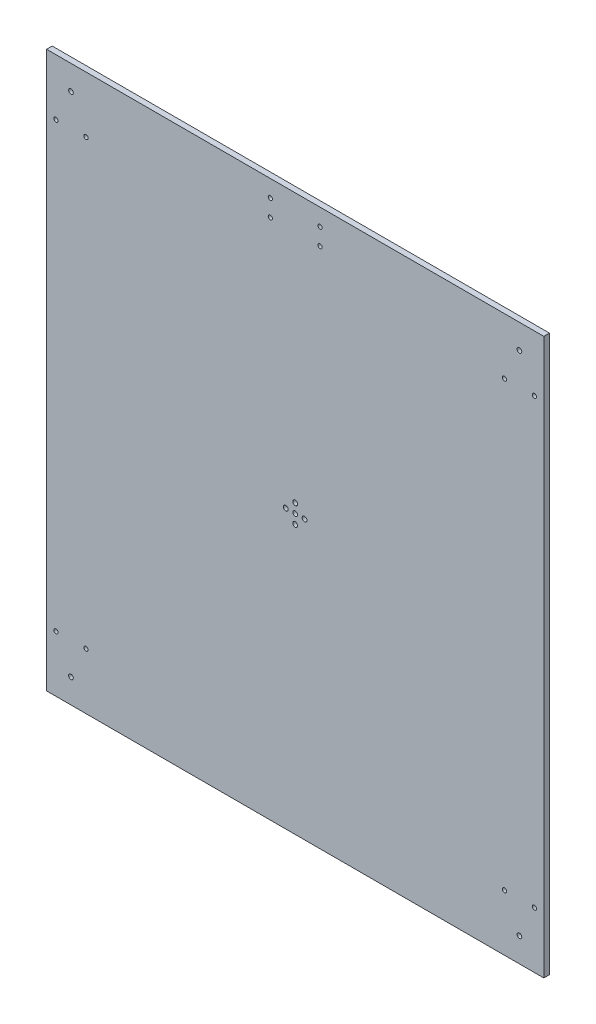
SolidWorks part; units mm, degrees
ref_plane "Спереди" through (0, 0, 0) normal (0, 0, 1) x (1, 0, 0)
ref_plane "Сверху" through (0, 0, 0) normal (0, 1, 0) x (1, 0, 0)
ref_plane "Справа" through (0, 0, 0) normal (1, 0, 0) x (0, 0, -1)
sketch "Эскиз3" plane through (0, 0, 0) normal (0, 0, 1) x (1, 0, 0)
  line L0 (0, 0) -> (0, 10) construction
  line L5 (265, -296.15) -> (-265, -296.15)
  line L6 (265, -296.15) -> (265, 296.15)
  line L7 (265, 296.15) -> (-265, 296.15)
  line L8 (-265, -296.15) -> (-265, 296.15)
  line L9 (0, 0) -> (10, 0) construction
  line L10 (0, 0) -> (0, -10) construction
  line L11 (0, 0) -> (-10, 0) construction
  circle A0 centre (0, 0) radius 2.55
  circle A1 centre (0, 10) radius 2.55
  circle A2 centre (10, 0) radius 2.55
  circle A3 centre (0, -10) radius 2.55
  circle A4 centre (-10, 0) radius 2.55
  point P0 (0, 0)
  point P5 (-265, 0)
  point P6 (0, 296.15)
  point P21 (0, 0)
  dimension "D3" = 5.1
  dimension "D4" = 5.1
  dimension "D1" = 592.3
  dimension "D2" = 530
  dimension "D5" = 10
  dimension "D6" = 4
extrude "Бобышка-Вытянуть1" add sketch "Эскиз3" along normal blind 6
sketch "Эскиз4" plane through (0, 0, 6) normal (0, 0, 1) x (1, 0, 0)
  line L0 (265, 296.15) -> (-265, 296.15) construction
  line L1 (-265, 296.15) -> (-265, -296.15) construction
  circle A0 centre (-239, 270.15) radius 2.5
  dimension "D1" = 5
  dimension "D2" = 26
  dimension "D3" = 26
extrude "Вырез-Вытянуть1" cut sketch "Эскиз4" against normal through all contours A0
pattern_linear "Линейный массив1" count 2 spacing 478 along (1, 0, 0) count 2 spacing 540.3 along (0, -1, 0) of "Вырез-Вытянуть1"
sketch "Эскиз7" plane through (0, 0, 0) normal (0, 0, -1) x (-1, 0, 0)
  line L9 (-26.5, 278.15) -> (26.5, 278.15) construction
  line L10 (-26.5, 278.15) -> (-26.5, 260.15) construction
  line L11 (-26.5, 260.15) -> (26.5, 260.15) construction
  line L16 (26.5, 278.15) -> (26.5, 260.15) construction
  line L17 (-265, 296.15) -> (265, 296.15) construction
  circle A0 centre (-26.5, 278.15) radius 2.25
  circle A1 centre (26.5, 278.15) radius 2.25
  circle A2 centre (-26.5, 260.15) radius 2.25
  circle A3 centre (26.5, 260.15) radius 2.25
  point P4 (0, 260.15)
  dimension "D4" = 4.5
  dimension "D5" = 4.5
  dimension "D6" = 4.5
  dimension "D7" = 4.5
  dimension "D1" = 53
  dimension "D2" = 18
  dimension "D3" = 18
extrude "Вырез-Вытянуть2" cut sketch "Эскиз7" against normal through all
sketch "Эскиз8" plane through (0, 0, 0) normal (0, 0, -1) x (-1, 0, 0)
  line L0 (223, 236.15) -> (255, 236.15) construction
  line L8 (265, 296.15) -> (265, -296.15) construction
  line L9 (-265, 296.15) -> (265, 296.15) construction
  circle A4 centre (223, 236.15) radius 2.25
  circle A5 centre (255, 236.15) radius 2.25
  dimension "D3" = 32
  dimension "D4" = 10
  dimension "D5" = 60
  dimension "D1" = 4.5
  dimension "D2" = 4.5
extrude "Вырез-Вытянуть3" cut sketch "Эскиз8" against normal through all
pattern_linear "Линейный массив2" count 2 spacing 472.3 along (0, -1, 0) count 2 spacing 478 along (1, 0, 0) of "Вырез-Вытянуть3"
equation "\"Ширина груза\"= 420"
equation "\"Глубина груза\"= 490"
equation "\"Высота груза\"= 297"
equation "\"Ширина ячейки\"= \"Ширина груза\" + 10"
equation "\"Глубина ячейки\"= \"Глубина груза\" + 10"
equation "\"Высота ячейки\"= \"Высота груза\" + 10 + 13"
equation "\"Колво ячеек ширина\"= 2"
equation "\"Колво ячеек высота\"= 2"
equation "\"Толщина стенки\" = 6"
equation "\"Крепление дверцы\"= 5 "
equation "\"Ширина рейки\"= \"Толщина шестерни\""
equation "\"Высота рейки\"= 20"
equation "\"Высота пола\"= \"Толщина стенки\" * 2"
equation "\"Колво полозьев\"= 5"
equation "\"Отступ рейки\"= 20"
equation "\"Глубина каретки\"= \"Глубина ячейки\" + 30 + \"Мотор Y высота корпуса\" + 20"
equation "\"Длинна рейки\" = (\"Ширина ячейки\" + \"Толщина стенки\" + \"Крепление дверцы\") * \"Колво ячеек ширина\" + \"Ширина ячейки выгрузки\" * \"Колво выгрузки\" + \"Толщина стенки\" + \"Отступ крепления мотора фиксации\" * 2 - \"Крепление дверцы\" * \"Колво ячеек ширина\""
equation "\"Отступ шпильки\"= 26"
equation "\"Диаметр шпильки\"= 5"
equation "\"D1@Бобышка-Вытянуть1\" = \"Толщина стенки\""
equation "\"D1@Эскиз4\"= \"Диаметр шпильки\""
equation "\"D2@Эскиз4\"=\"Отступ шпильки\""
equation "\"D3@Эскиз4\"= \"Отступ шпильки\""
equation "\"D2@Эскиз3\"=\"Ширина ячейки\" + \"Ширина пластины\" * 2"
equation "\"D1@Эскиз3\"=\"Глубина каретки\" "
equation "\"D3@Линейный массив1\"=\"Ширина ячейки\"  +\"Ширина пластины\" *2 - \"Отступ шпильки\" * 2"
equation "\"D4@Линейный массив1\"=\"Глубина каретки\" + \"Ширина рейки\" * 2 - \"Отступ шпильки\" * 2 - \"Ширина рейки\" * 2"
equation "\"Длинна шпильки\"= ( \"Высота ячейки\" + \"Толщина стенки\" + \"Высота пола\" ) * \"Колво ячеек высота\" + ( \"Толщина стенки\" + \"Отступ рейки\" ) * 2 "
equation "\"Ширина пластины\"= 50  "
equation "\"Высота зона выгрузки\"= \"Высота ячейки\" * 2 + \"Толщина стенки\" * 2"
equation "\"Колво выгрузки\"= 1"
equation "\"Отступ крепления мотора фиксации\" = (\"Ширина пластины\" + 20 - \"Толщина стенки\") / 2"
equation "\"Мотор X ширина корпуса\"= 42.3"
equation "\"Мотор X высота корпуса\"= 42.3"
equation "\"Мотор X длина корпуса\"= 40"
equation "\"Мотор X вылет вала\"= 19.8"
equation "\"Мотор Y ширина корпуса\"= 42.3"
equation "\"Мотор Y высота корпуса\"= 42.3"
equation "\"Мотор Y длина корпуса\"= 48"
equation "\"Мотор Y вылет вала\"= 30"
equation "\"Мотор Z ширина корпуса\"= 42"
equation "\"Мотор Z высота корпуса\"= 42"
equation "\"Мотор Z длина корпуса\"= 40"
equation "\"Мотор Z вылет вала\"= 23"
equation "\"Мотор диаметр вала ПРЕДВ\"= 5"
equation "\"Мотор шаг крепления ПРЕДВ\"= 31"
equation "\"Мотор диаметр отверстий ПРЕДВ\"= 3"
equation "\"Мотор глубина отверстий ПРЕДВ\"= 4.5"
equation "\"Мотор диаметр буртика ПРЕДВ\"= 22"
equation "\"Мотор высота буртика ПРЕДВ\"= 2"
equation "\"Мотор диаметр шкива ПРЕДВ\"= 16"
equation "\"Мотор длина шкива ПРЕДВ\"= 12"
equation "\"Мотор отступ шкива ПРЕДВ\"= 5"
equation "\"Мотор X шаг градусов\"= 1.8"
equation "\"Мотор Y шаг градусов\"= 1.8"
equation "\"Мотор Z шаг градусов\"= 1.8"
equation "\"Мотор Y диаметр ротора\"= 25.78"
equation "\"Толщина шестерни\"= 10"
equation "\"Ширина ячейки выгрузки\"= \"Ширина ячейки\" + \"Толщина стенки\" + \"Отступ крепления мотора фиксации\"*2"
equation "\"D3@Линейный массив2\"=592.3-60*2"
equation "\"D4@Линейный массив2\"=530 - 26*2"
